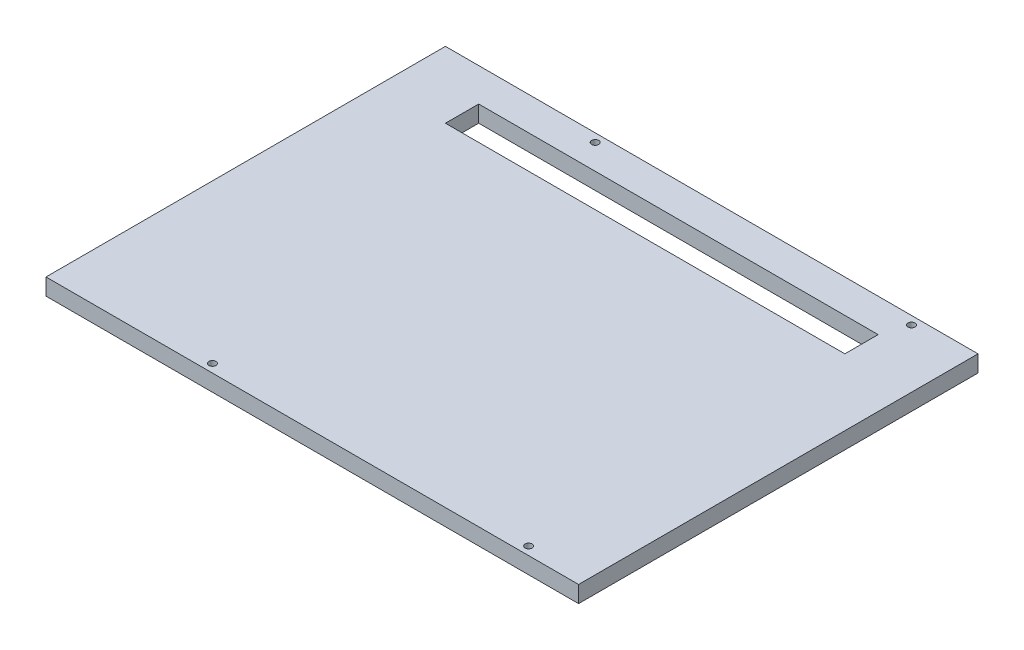
SolidWorks part; units mm, degrees
ref_plane "Front Plane" through (0, 0, 0) normal (0, 0, 1) x (1, 0, 0)
ref_plane "Top Plane" through (0, 0, 0) normal (0, 1, 0) x (1, 0, 0)
ref_plane "Right Plane" through (0, 0, 0) normal (1, 0, 0) x (0, 0, -1)
sketch "Sketch2" plane through (0, 0, 0) normal (0, 1, 0) x (1, 0, 0)
  line L1 (-101.6, -76.2) -> (101.6, -76.2)
  line L2 (-101.6, -76.2) -> (-101.6, 76.2)
  line L3 (-101.6, 76.2) -> (101.6, 76.2)
  line L4 (101.6, -76.2) -> (101.6, 76.2)
  line L5 (-101.6, -76.2) -> (101.6, 76.2) construction
  line L6 (-101.6, 76.2) -> (101.6, -76.2) construction
  point P0 (0, 0)
  dimension "D1" = 203.2
  dimension "D2" = 152.4
extrude "Boss-Extrude1" add sketch "Sketch2" along normal blind 6.35
sketch "Sketch3" plane through (0, 6.35, 0) normal (0, 1, 0) x (1, 0, 0)
  line L0 (-101.6, 0) -> (101.6, 0) construction
  line L1 (-101.6, 76.2) -> (-101.6, -76.2) construction
  line L2 (101.6, -76.2) -> (101.6, 76.2) construction
  line L3 (0, 76.2) -> (0, -76.2) construction
  line L4 (101.6, 76.2) -> (-101.6, 76.2) construction
  line L5 (-101.6, -76.2) -> (101.6, -76.2) construction
  line L7 (-76.2, 63.5) -> (76.2, 63.5)
  line L8 (-76.2, 63.5) -> (-76.2, 50.8)
  line L9 (-76.2, 50.8) -> (76.2, 50.8)
  line L10 (76.2, 63.5) -> (76.2, 50.8)
  line L11 (-76.2, 63.5) -> (76.2, 50.8) construction
  line L12 (-76.2, 50.8) -> (76.2, 63.5) construction
  point P12 (0, 57.15)
  dimension "D1" = 12.7
  dimension "D2" = 152.4
  dimension "D3" = 12.7
extrude "Cut-Extrude1" cut sketch "Sketch3" against normal blind 6.35
sketch "Sketch4" plane through (0, 0, 0) normal (0, -1, 0) x (1, 0, 0)
  line L0 (-101.6, -76.2) -> (-101.6, 76.2) construction
  line L1 (-101.6, 50.8) -> (-76.2, 50.8)
  line L2 (-101.6, 50.8) -> (-101.6, 25.4)
  line L3 (-101.6, 25.4) -> (-76.2, 25.4)
  line L4 (-76.2, 50.8) -> (-76.2, 25.4)
  line L5 (0, 76.2) -> (0, -76.2) construction
  line L6 (-101.6, 76.2) -> (101.6, 76.2) construction
  line L7 (101.6, -76.2) -> (-101.6, -76.2) construction
  line L8 (-101.6, 0) -> (101.6, 0) construction
  line L9 (101.6, 76.2) -> (101.6, -76.2) construction
  line L10 (101.6, 25.4) -> (76.2, 25.4)
  line L11 (76.2, 50.8) -> (76.2, 25.4)
  line L12 (101.6, 50.8) -> (76.2, 50.8)
  line L13 (101.6, 50.8) -> (101.6, 25.4)
  line L14 (101.6, -50.8) -> (101.6, -25.4)
  line L15 (101.6, -50.8) -> (76.2, -50.8)
  line L16 (76.2, -50.8) -> (76.2, -25.4)
  line L17 (101.6, -25.4) -> (76.2, -25.4)
  line L18 (-101.6, -25.4) -> (-76.2, -25.4)
  line L19 (-76.2, -50.8) -> (-76.2, -25.4)
  line L20 (-101.6, -50.8) -> (-76.2, -50.8)
  line L21 (-101.6, -50.8) -> (-101.6, -25.4)
  dimension "D1" = 25.4
  dimension "D2" = 25.4
  dimension "D3" = 25.4
sketch "Sketch6" plane through (0, 0, 0) normal (0, -1, 0) x (1, 0, 0)
  line L0 (0, -50.8) -> (0, -63.5) construction
  line L1 (-76.2, -50.8) -> (76.2, -50.8) construction
  line L2 (76.2, -63.5) -> (-76.2, -63.5) construction
ref_plane "Plane1" through (0, 0, 0) normal (-1, 0, 0) x (0, 0, 1)
sketch "Sketch12" plane through (0, 6.35, 0) normal (0, 1, 0) x (1, 0, 0)
  line L0 (101.6, 76.2) -> (-101.6, 76.2) construction
  line L1 (-38.1204, 76.2) -> (25.3796, 76.2)
  line L2 (-38.1204, 76.2) -> (-38.1204, 63.5)
  line L3 (-38.1204, 63.5) -> (25.3796, 63.5)
  line L4 (25.3796, 76.2) -> (25.3796, 63.5)
  line L5 (76.2, 63.5) -> (-76.2, 63.5) construction
  dimension "D1" = 63.5
hole_wizard "#6-32 Tapped Hole1" positions "Sketch13" profile "Sketch14" tap size "#6-32" standard "ANSI Inch"
sketch "Sketch13" plane through (0, 6.35, 0) normal (0, 1, 0) x (1, 0, 0)
  point P12 (-41.275, -73.025)
  point P15 (-41.275, 73.025)
  point P18 (79.375, 73.025)
  point P21 (79.375, -73.025)
cosmetic thread "Hole Thread6" parameters "D1"=11.43, "D2"=3.5052
cosmetic thread "Hole Thread7" parameters "D1"=11.43, "D2"=3.5052
cosmetic thread "Hole Thread8" parameters "D1"=11.43, "D2"=3.5052
cosmetic thread "Hole Thread9" parameters "D1"=11.43, "D2"=3.5052
sketch "Sketch14" plane through (-41.275, 6.35, 73.025) normal (1, 0, 0) x (0, 0, 1)
  line L0 (0, 0) -> (0, 13.5127)
  line L1 (0, 13.5127) -> (1.3525, 12.7)
  line L2 (1.3525, 12.7) -> (1.3525, 0)
  line L5 (1.3525, 0) -> (0, 0)
  line L10 (0, 13.5127) -> (-1.3526, 12.7) construction
  line L11 (0, -6.35) -> (0, 107.95) construction
  dimension "Tap Drill Dia." = 2.7051
  dimension "Tap Drill Depth" = 12.7
  dimension "Drill Angle" = 118
